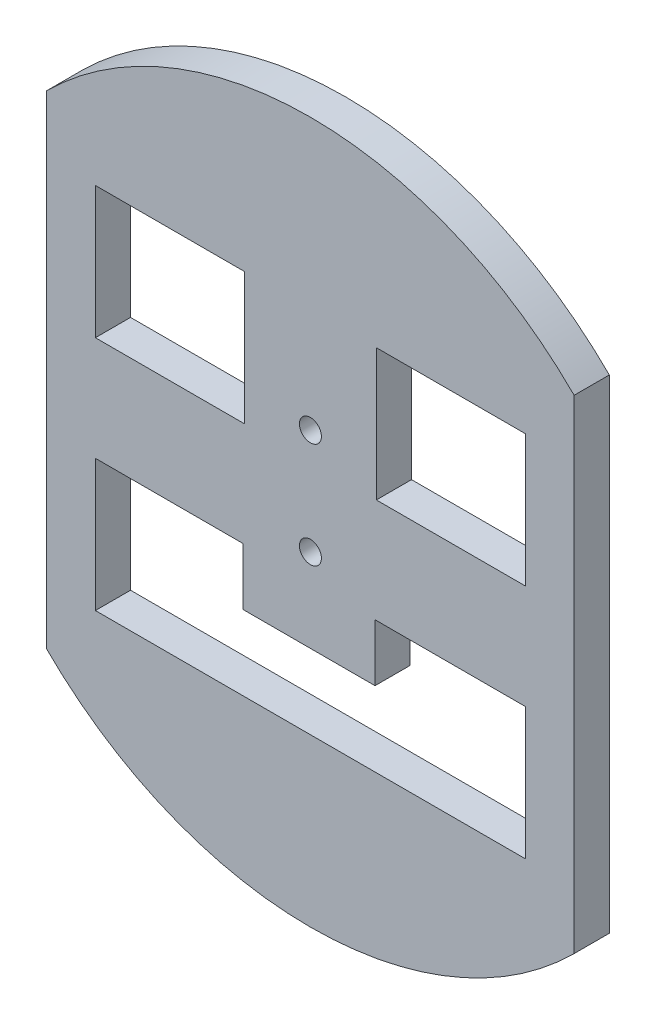
SolidWorks part; units mm, degrees
material "ABS"
ref_plane "Plano frontal" through (0, 0, 0) normal (0, 0, 1) x (1, 0, 0)
ref_plane "Plano superior" through (0, 0, 0) normal (0, 1, 0) x (1, 0, 0)
ref_plane "Plano direito" through (0, 0, 0) normal (1, 0, 0) x (0, 0, -1)
sketch "Esboço1" plane through (0, 0, 0) normal (0, 0, 1) x (1, 0, 0)
  line L0 (0, 0) -> (0, -110)
  line L1 (120, -110) -> (120, 0)
  line L2 (60, -12.6598) -> (60, -97.3402) construction
  line L3 (120, -55) -> (-37.4329, -55) construction
  line L8 (12.1875, -86.875) -> (107.8125, -23.125) construction
  line L9 (12.1875, -23.125) -> (107.8125, -86.875) construction
  arc A4 (0, 0) -> (120, 0) centre (60, -60.208) cw
  arc A5 (0, -110) -> (120, -110) centre (60, -49.792) ccw
  point P9 (60, -55)
  point P17 (60, 24.792)
  dimension "D1" = 110
  dimension "D5" = 85
  dimension "D2" = 63.75
  dimension "D3" = 95.625
extrude "Ressalto-extrusão1" add sketch "Esboço1" along normal blind 8
sketch "Esboço2" plane through (0, 0, 0) normal (0, 0, -1) x (-1, 0, 0)
  line L0 (-60, 24.792) -> (-60, -134.792) construction
  line L1 (-120, -55) -> (0, -55) construction
  line L2 (-120, -110) -> (-120, 0) construction
  line L3 (0, 0) -> (0, -110) construction
  line L4 (-108.9196, -96.875) -> (-11.0804, -96.875)
  line L5 (-108.9196, -43.125) -> (-75, -43.125)
  line L6 (-108.9196, -43.125) -> (-108.9196, -13.125)
  line L7 (-108.9196, -13.125) -> (-11.0804, -13.125)
  line L8 (-11.0804, -43.125) -> (-11.0804, -13.125)
  line L11 (-11.0804, -66.875) -> (-11.0804, -96.875)
  line L12 (-108.9196, -66.875) -> (-74.6956, -66.875)
  line L13 (-108.9196, -66.875) -> (-108.9196, -96.875)
  line L14 (-75, -43.125) -> (-75, -30.609)
  line L15 (-75, -30.609) -> (-45, -30.609)
  line L16 (-45, -30.609) -> (-45, -43.125)
  line L18 (-44.6956, -79.875) -> (-74.6956, -79.875)
  line L19 (-74.6956, -79.875) -> (-74.6956, -66.875)
  line L20 (-44.6956, -66.875) -> (-44.6956, -79.875)
  line L21 (-45, -43.125) -> (-11.0804, -43.125)
  line L22 (-44.6956, -66.875) -> (-11.0804, -66.875)
  arc A0 (0, 0) -> (-120, 0) centre (-60, -60.208) ccw construction
  arc A1 (-120, -110) -> (0, -110) centre (-60, -49.792) ccw construction
  point P14 (-60, -30.125)
  point P24 (-60, -79.875)
  point P26 (-60, -30.609)
  dimension "D1" = 30
  dimension "D2" = 83.75
  dimension "D3" = 30
  dimension "D4" = 30
  dimension "D6" = 97.8393
  dimension "D7" = 13
extrude "Corte-extrusão1" cut sketch "Esboço2" against normal blind 10 contours L6 L7 L8 L21 L16 L15 L14 L5 | L4 L11 L22 L20 L18 L19 L12 L13
sketch "Esboço3" plane through (0, -30.609, 0) normal (0, 1, 0) x (1, 0, 0)
  line L4 (75, -8) -> (75, 0)
  line L5 (75, 0) -> (45, 0)
  line L6 (45, 0) -> (45, -8)
  line L7 (45, -8) -> (75, -8)
  line L8 (75, -8) -> (75, 0)
  line L9 (75, 0) -> (45, 0)
  line L10 (45, 0) -> (45, -8)
  line L11 (45, -8) -> (75, -8)
  dimension "D1" = 0
extrude "Ressalto-extrusão2" add sketch "Esboço3" along normal up to next
sketch "Esboço4" plane through (0, 0, 0) normal (0, 0, -1) x (-1, 0, 0)
  circle A0 centre (-15.0938, 0) radius 2.5
  circle A1 centre (-6.0938, -33.44) radius 2.5
  circle A2 centre (-6.0938, -75.315) radius 2.5
  circle A3 centre (-18.7084, -112.188) radius 2.5
  circle A4 centre (-60, -124.1876) radius 2.5
  circle A5 centre (-101.2916, -112.188) radius 2.5
  circle A6 centre (-113.9062, -75.315) radius 2.5
  circle A7 centre (-113.9062, -33.44) radius 2.5
  circle A8 centre (-104.9062, 0) radius 2.5
  dimension "D1" = 5
extrude "Corte-extrusão2" cut sketch "Esboço4" against normal blind 3
sketch "Esboço5" plane through (0, 0, 8) normal (0, 0, 1) x (1, 0, 0)
  line L0 (60, 24.792) -> (60, -134.792) construction
  line L1 (44.6956, -48.875) -> (75, -48.875) construction
  line L4 (44.6956, -79.875) -> (74.6956, -79.875) construction
  line L5 (44.6956, -79.875) -> (75, -79.875)
  line L6 (44.6956, -79.875) -> (44.6956, -17.875)
  line L7 (44.6956, -17.875) -> (75, -17.875)
  line L8 (75, -79.875) -> (75, -17.875)
  line L9 (44.6956, -66.875) -> (44.6956, -79.875) construction
  line L10 (75, -43.125) -> (75, -13.125) construction
  arc A0 (120, 0) -> (0, 0) centre (60, -60.208) ccw construction
  arc A1 (0, -110) -> (120, -110) centre (60, -49.792) ccw construction
  circle A2 centre (60, -60.875) radius 2.5
  circle A4 centre (60, -36.875) radius 2.5
  dimension "D1" = 5
  dimension "D2" = 12
  dimension "D3" = 62
extrude "Corte-extrusão3" cut sketch "Esboço5" against normal blind 5 contours A4 | A2
